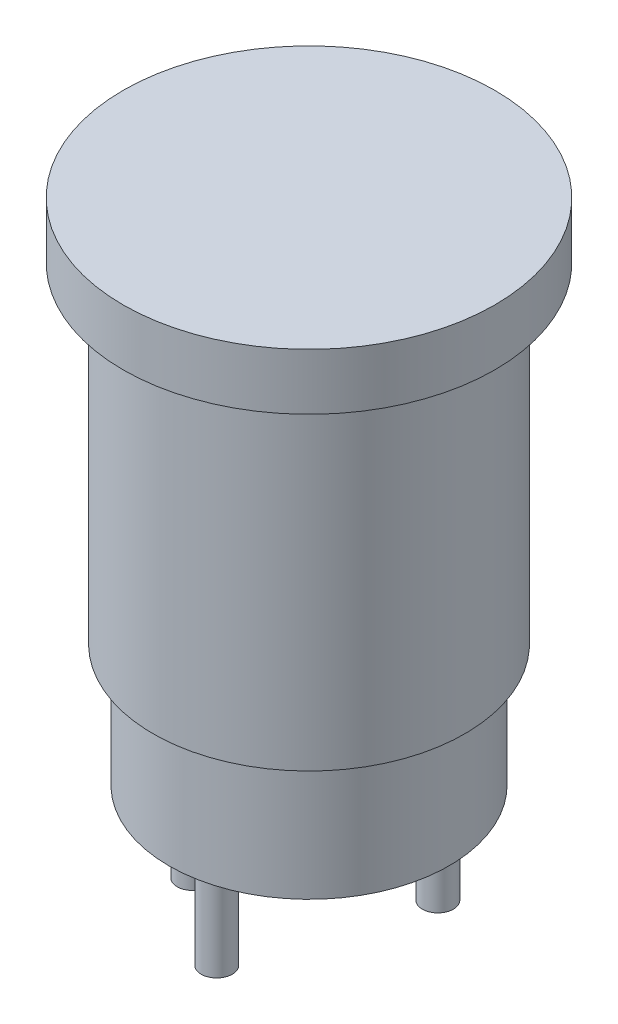
SolidWorks part; units mm, degrees
ref_plane "Front Plane" through (0, 0, 0) normal (0, 0, 1) x (1, 0, 0)
ref_plane "Top Plane" through (0, 0, 0) normal (0, 1, 0) x (1, 0, 0)
ref_plane "Right Plane" through (0, 0, 0) normal (1, 0, 0) x (0, 0, -1)
sketch "Sketch1" plane through (0, 0, 0) normal (0, 0, 1) x (1, 0, 0)
  line L0 (0, 0) -> (7.6, 0)
  line L1 (0, -55) -> (0, 55) construction
  line L2 (7.6, 0) -> (7.6, -2.3)
  line L3 (7.6, -2.3) -> (6.375, -2.3)
  line L4 (6.375, -2.3) -> (6.375, -15.8)
  line L5 (6.375, -15.8) -> (5.7284, -15.8)
  line L6 (5.7284, -15.8) -> (5.7284, -20.8)
  line L7 (5.7284, -20.8) -> (0, -20.8)
  line L8 (0, -20.8) -> (0, 0)
  dimension "D1" = 7.6
  dimension "D2" = 6.375
  dimension "D3" = 13.5
  dimension "D4" = 2.3
  dimension "D5" = 20.8
revolve "Revolve1" add sketch "Sketch1" angle 360 about L8
sketch "Sketch2" plane through (0, -20.8, 0) normal (0, -1, 0) x (1, 0, 0)
  circle A0 centre (0, 3.7731) radius 0.635
  dimension "D1" = 1.27
extrude "Boss-Extrude1" add sketch "Sketch2" along normal blind 4.5
pattern_circular "CirPattern1" count 4 every 72 about axis through (0, -20.8, 0) along (0, -1, 0) of "Boss-Extrude1"
